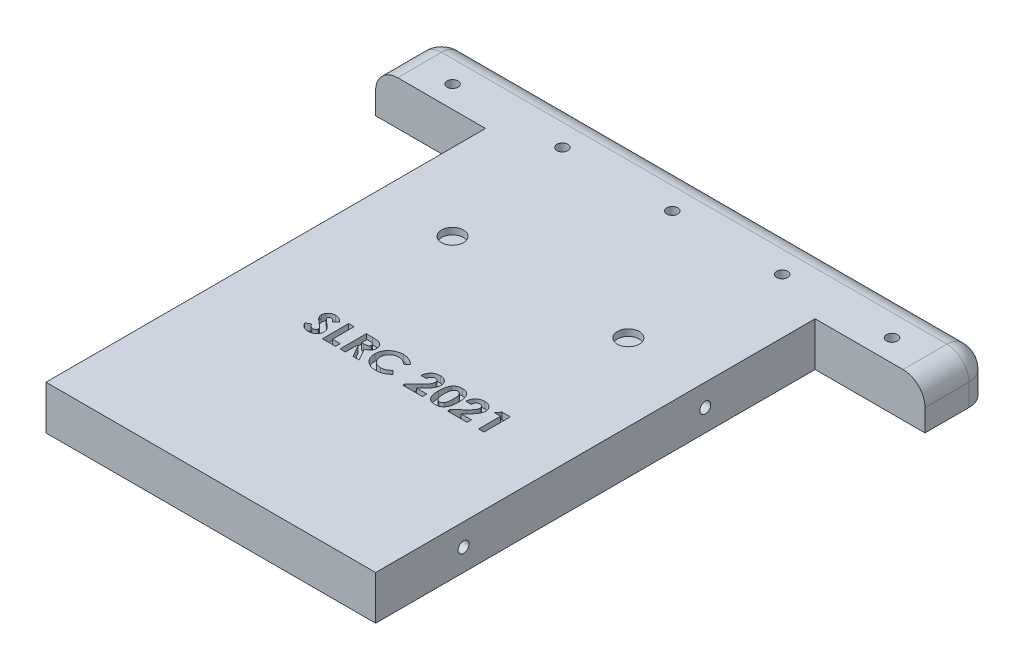
SolidWorks part; units mm, degrees
ref_plane "Front Plane" through (0, 0, 0) normal (0, 0, 1) x (1, 0, 0)
ref_plane "Top Plane" through (0, 0, 0) normal (0, 1, 0) x (1, 0, 0)
ref_plane "Right Plane" through (0, 0, 0) normal (1, 0, 0) x (0, 0, -1)
sketch "Sketch1" plane through (0, 0, 0) normal (0, 1, 0) x (1, 0, 0)
  line L0 (-75, -100) -> (75, -100)
  line L1 (75, -100) -> (75, 100)
  line L2 (75, 100) -> (125, 100)
  line L3 (125, 100) -> (125, 130)
  line L4 (125, 130) -> (-125, 130)
  line L5 (-125, 130) -> (-125, 100)
  line L6 (-125, 100) -> (-75, 100)
  line L7 (-75, 100) -> (-75, -100)
  point P7 (0, -100)
  point P9 (-75, 0)
  dimension "D1" = 250
  dimension "D2" = 30
  dimension "D3" = 150
  dimension "D4" = 200
extrude "Boss-Extrude1" add sketch "Sketch1" along normal blind 20
sketch "Sketch2" plane through (-75, 0, 0) normal (-1, 0, 0) x (0, 0, 1)
  line L0 (100, 20) -> (100, 0) construction
  circle A0 centre (60, 10) radius 2.5
  circle A1 centre (-50, 10) radius 2.5
  point P6 (100, 10)
  dimension "D1" = 5
  dimension "D2" = 40
  dimension "D3" = 110
extrude "Cut-Extrude1" cut sketch "Sketch2" against normal through all
sketch "Sketch4" plane through (0, 0, 0) normal (0, -1, 0) x (1, 0, 0)
  line L0 (-125, -115) -> (125, -115) construction
  line L1 (-125, -130) -> (-125, -100) construction
  line L2 (125, -100) -> (125, -130) construction
  line L3 (0, -11) -> (0, 11) construction
  circle A0 centre (-100, -115) radius 2.5
  circle A1 centre (-50, -115) radius 2.5
  circle A2 centre (0, -115) radius 2.5
  circle A3 centre (50, -115) radius 2.5
  circle A4 centre (100, -115) radius 2.5
  dimension "D1" = 5
  dimension "D2" = 25
  dimension "D3" = 50
extrude "Cut-Extrude2" cut sketch "Sketch4" against normal blind 5
fillet "Fillet1" radius 10 2 edges at (125, 10, -130) (-125, 10, -130)
fillet "Fillet2" radius 10 5 edges at (125, 20, -110) (122.0711, 20, -127.0711) (-125, 20, -110) (-122.0711, 20, -127.0711) (0, 20, -130)
sketch "Sketch6" plane through (0, 20, 0) normal (0, 1, 0) x (1, 0, 0)
  line L0 (115, 110) -> (-115, 110) construction
  line L1 (115, 100) -> (115, 120) construction
  line L2 (-115, 120) -> (-115, 100) construction
  line L3 (0, -11) -> (0, 11) construction
  circle A0 centre (0, 110) radius 2.5
  circle A1 centre (50, 110) radius 2.5
  circle A2 centre (100, 110) radius 2.5
  circle A3 centre (-50, 110) radius 2.5
  circle A4 centre (-100, 110) radius 2.5
  dimension "D1" = 5
  dimension "D2" = 50
  dimension "D3" = 50
extrude "Cut-Extrude3" cut sketch "Sketch6" against normal blind 5
sketch "Sketch7" plane through (0, 20, 0) normal (0, 1, 0) x (1, 0, 0)
  line L0 (-40, -20) -> (40, -20) construction
  line L1 (-75, -100) -> (75, -100) construction
  line L2 (0, -12.1) -> (0, 12.1) construction
  text T0 "<b>SLRC 2021</b>" font "Century Gothic" height 12
  point P5 (0, -20)
  dimension "D1" = 80
  dimension "D2" = 80
extrude "Cut-Extrude4" cut sketch "Sketch7" against normal blind 3
sketch "Sketch8" plane through (0, 20, 0) normal (0, 1, 0) x (1, 0, 0)
  line L0 (-75, 100) -> (-75, -100) construction
  line L1 (-75, -100) -> (75, -100) construction
  line L2 (0, -11) -> (0, 11) construction
  circle A0 centre (-40, 50) radius 5
  circle A1 centre (40, 50) radius 5
  dimension "D1" = 10
  dimension "D2" = 35
  dimension "D3" = 150
extrude "Cut-Extrude5" cut sketch "Sketch8" against normal blind 3
